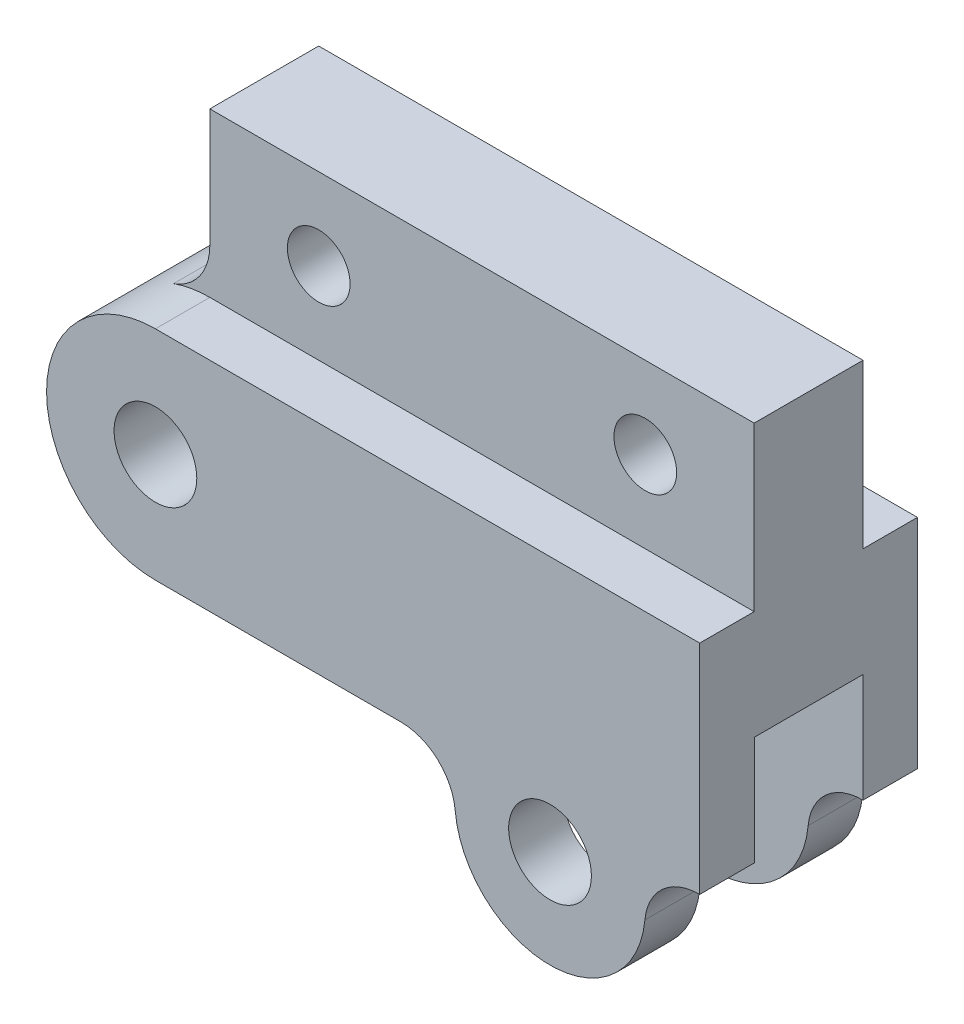
SolidWorks part; units mm, degrees
material "Nylon 101"
ref_plane "Front Plane" through (0, 0, 0) normal (0, 0, 1) x (1, 0, 0)
ref_plane "Top Plane" through (0, 0, 0) normal (0, 1, 0) x (1, 0, 0)
ref_plane "Right Plane" through (0, 0, 0) normal (1, 0, 0) x (0, 0, -1)
sketch "Sketch1" plane through (0, 0, 0) normal (0, 0, 1) x (1, 0, 0)
  line L0 (-19.05, 0) -> (19.05, 0) construction
  line L1 (19.05, -6.35) -> (-19.05, -6.35)
  line L2 (19.05, -6.35) -> (19.05, 6.35)
  line L3 (19.05, 6.35) -> (-19.05, 6.35)
  line L4 (-19.05, 6.35) -> (-19.05, -6.35)
  line L5 (15.875, -14.2875) -> (15.875, -6.35)
  line L6 (15.875, -14.2875) -> (4.7625, -14.2875)
  line L7 (4.7625, -14.2875) -> (4.7625, -6.35)
  line L9 (0, 6.35) -> (0, -6.35) construction
  point P0 (0, 0)
  dimension "D3" = 11.1125
  dimension "D1" = 38.1
  dimension "D2" = 12.7
  dimension "D4" = 7.9375
  dimension "D5" = 3.175
extrude "Boss-Extrude1" add sketch "Sketch1" along normal mid plane 12.7 contours L7 L6 L1 | L3 L4 L1 L2 region at (0, 0, 0) region at (10.3188, -10.3187, 0)
sketch "Sketch2" plane through (0, 0, 0) normal (0, 0, 1) x (1, 0, 0)
  line L0 (-6.35, 15.875) -> (-6.35, 6.35) construction
  line L1 (19.05, 6.35) -> (-12.7, 6.35)
  line L2 (19.05, 6.35) -> (19.05, 15.875)
  line L3 (19.05, 15.875) -> (-12.7, 15.875)
  line L4 (-12.7, 6.35) -> (-12.7, 15.875)
  line L5 (12.7, 15.875) -> (12.7, 6.35) construction
  line L6 (3.175, 15.875) -> (3.175, 6.35) construction
  dimension "D1" = 9.525
  dimension "D2" = 19.05
  dimension "D3" = 6.35
extrude "Boss-Extrude2" add sketch "Sketch2" along normal mid plane 6.35
hole_wizard "#6 Clearance Hole1" positions "Sketch4" profile "Sketch3" hole size "#6" standard "ANSI Inch" end condition through all
sketch "Sketch4" plane through (0, 0, 3.175) normal (0, 0, 1) x (1, 0, 0)
  line L0 (3.175, 15.875) -> (3.175, 6.35) construction
  line L1 (19.05, 15.875) -> (-12.7, 15.875) construction
  line L6 (19.05, 6.35) -> (19.05, 15.875) construction
  line L9 (-6.35, 11.1125) -> (12.7, 11.1125) construction
  line L10 (-12.7, 6.35) -> (19.05, 6.35) construction
  point P0 (-6.35, 11.1125)
  point P2 (12.7, 11.1125)
  dimension "D1" = 6.35
sketch "Sketch3" plane through (-6.35, 11.1125, 3.175) normal (1, 0, 0) x (0, -1, 0)
  line L0 (0, 0) -> (0, 9.525)
  line L1 (0, 9.525) -> (1.8288, 9.525)
  line L2 (1.8288, 9.525) -> (1.8288, 0)
  line L5 (1.8288, 0) -> (0, 0)
  line L11 (0, -6.35) -> (0, 107.95) construction
  dimension "Thru Hole Dia." = 3.6576
  dimension "Thru Hole Depth" = 9.525
hole_wizard "3/16 (0.1875) Clearance Dowel Hole1" positions "Sketch6" profile "Sketch5" hole size "3/16" standard "ANSI Inch" end condition through all
sketch "Sketch6" plane through (0, 0, 6.35) normal (0, 0, 1) x (1, 0, 0)
  line L1 (-19.05, 6.35) -> (-19.05, -6.35) construction
  line L2 (10.3188, -14.2875) -> (10.3188, 6.35) construction
  line L3 (15.875, -14.2875) -> (4.7625, -14.2875) construction
  line L4 (19.05, 6.35) -> (-19.05, 6.35) construction
  point P2 (-12.7, 0)
  point P11 (-19.05, 0)
  point P14 (10.3188, -8.5725)
  dimension "D1" = 6.35
  dimension "D2" = 5.715
sketch "Sketch5" plane through (-12.7, 0, 6.35) normal (1, 0, 0) x (0, -1, 0)
  line L0 (0, 0) -> (0, 12.7)
  line L1 (0, 12.7) -> (2.413, 12.7)
  line L2 (2.413, 12.7) -> (2.413, 0)
  line L5 (2.413, 0) -> (0, 0)
  line L11 (0, -6.35) -> (0, 107.95) construction
  dimension "Thru Hole Dia." = 4.826
  dimension "Thru Hole Depth" = 12.7
sketch "Sketch8" plane through (0, 0, 0) normal (0, 0, 1) x (1, 0, 0)
  line L0 (19.05, -6.35) -> (19.05, 6.35) construction
  line L1 (1.5875, -14.2875) -> (19.05, -14.2875)
  line L2 (1.5875, -14.2875) -> (1.5875, 0)
  line L3 (1.5875, 0) -> (19.05, 0)
  line L4 (19.05, -14.2875) -> (19.05, 0)
  line L5 (19.05, 6.35) -> (-19.05, 6.35) construction
  line L6 (15.875, -14.2875) -> (4.7625, -14.2875) construction
  dimension "D1" = 6.35
  dimension "D2" = 17.4625
extrude "Cut-Extrude3" cut sketch "Sketch8" against normal offset from surface 3.175 and the other way offset from surface 3.2004 up to face at (-10.287, 0, -6.35) other way up to face at (-10.287, 0, 6.35)
fillet "Fillet2" 2 edges at (4.7625, -14.2875, 4.7498) (15.875, -14.2875, 4.7498) type full round first side face at (4.7625, -10.3187, 4.7498) second side face at (15.875, -10.3187, 4.7498) middle face at (10.3188, -14.2875, 4.7498)
fillet "Fillet3" 2 edges at (4.7625, -14.2875, -4.7625) (15.875, -14.2875, -4.7625) type full round first side face at (4.7625, -10.3187, -4.7625) second side face at (15.875, -10.3187, -4.7625) middle face at (10.3188, -14.2875, -4.7625)
fillet "Fillet5" radius 3.175 4 edges at (15.875, -6.35, 4.7498) (15.875, -6.35, -4.7625) (4.7625, -6.35, -4.7625) (4.7625, -6.35, 4.7498) tangent propagation no
fillet "Fillet7" 2 edges at (-19.05, 6.35, 0) (-19.05, -6.35, 0) type full round first side face at (-2.3812, 6.35, 0.3969) second side face at (-3.5538, -6.35, -0.0064) middle face at (-19.05, 0, 0)
fillet "Fillet8" radius 3.175 1 edges at (-12.7, 6.35, 0)
